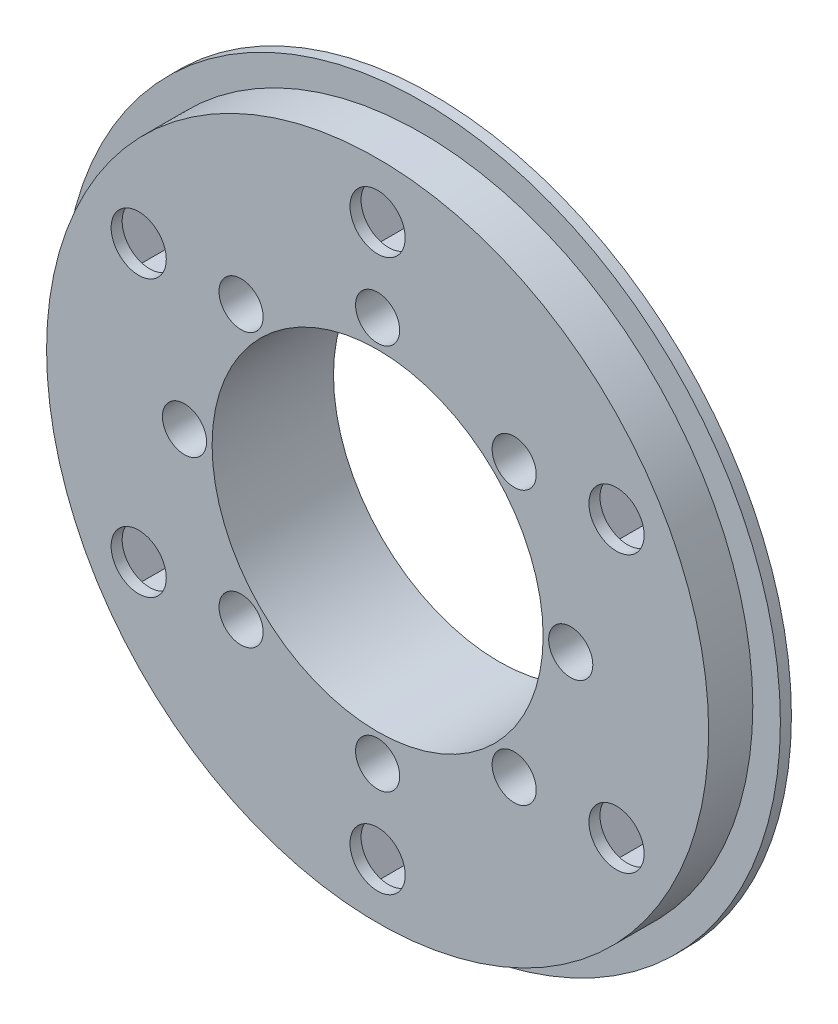
SolidWorks part; units mm, degrees
ref_plane "Front Plane" through (0, 0, 0) normal (0, 0, 1) x (1, 0, 0)
ref_plane "Top Plane" through (0, 0, 0) normal (0, 1, 0) x (1, 0, 0)
ref_plane "Right Plane" through (0, 0, 0) normal (1, 0, 0) x (0, 0, -1)
sketch "Sketch1" plane through (0, 0, 0) normal (0, 0, 1) x (1, 0, 0)
  circle A0 centre (0, 0) radius 20
  dimension "D1" = 40
extrude "Boss-Extrude1" add sketch "Sketch1" along normal blind 6
sketch "Sketch2" plane through (0, 0, 6) normal (0, 0, 1) x (1, 0, 0)
  circle A0 centre (0, 17.5) radius 2
  circle A1 centre (12.3744, 12.3744) radius 2
  circle A2 centre (17.5, 0) radius 2
  circle A3 centre (12.3744, -12.3744) radius 2
  circle A4 centre (0, -17.5) radius 2
  circle A5 centre (-12.3744, -12.3744) radius 2
  circle A6 centre (-17.5, 0) radius 2
  circle A7 centre (-12.3744, 12.3744) radius 2
  point P20 (0, 0)
  dimension "D1" = 4
  dimension "D2" = 17.5
  dimension "D3" = 8
extrude "Cut-Extrude1" cut sketch "Sketch2" against normal through all and the other way blind 7
sketch "Sketch3" plane through (0, 0, 0) normal (0, 0, -1) x (-1, 0, 0)
  circle A0 centre (0, 0) radius 15
  dimension "D1" = 30
extrude "Cut-Extrude2" cut sketch "Sketch3" against normal blind 6
sketch "Sketch4" plane through (0, 0, 6) normal (0, 0, 1) x (1, 0, 0)
  circle A0 centre (0, 0) radius 15
  circle A1 centre (0, 0) radius 30
  dimension "D1" = 60
extrude "Boss-Extrude2" add sketch "Sketch4" along normal blind 5
sketch "Sketch6" plane through (0, 0, 6) normal (0, 0, -1) x (-1, 0, 0)
  circle A0 centre (0, 17.5) radius 2
  circle A1 centre (12.3744, 12.3744) radius 2
  circle A2 centre (17.5, 0) radius 2
  circle A3 centre (12.3744, -12.3744) radius 2
  circle A4 centre (0, -17.5) radius 2
  circle A5 centre (-12.3744, -12.3744) radius 2
  circle A6 centre (-17.5, 0) radius 2
  circle A7 centre (-12.3744, 12.3744) radius 2
  point P19 (0, 0)
  dimension "D1" = 8
extrude "Cut-Extrude3" cut sketch "Sketch6" against normal blind 7
sketch "Sketch7" plane through (0, 0, 6) normal (0, 0, -1) x (-1, 0, 0)
  line L0 (23.96, 8.5) -> (26.2694, 12.5)
  line L1 (4.6188, 25) -> (2.3094, 29)
  line L2 (2.3094, 29) -> (-2.3094, 29)
  line L3 (-2.3094, 29) -> (-4.6188, 25)
  line L4 (-4.6188, 25) -> (-2.3094, 21)
  line L5 (-2.3094, 21) -> (2.3094, 21)
  line L6 (2.3094, 21) -> (4.6188, 25)
  line L7 (26.2694, 12.5) -> (23.96, 16.5)
  line L8 (23.96, 16.5) -> (19.3412, 16.5)
  line L9 (19.3412, 16.5) -> (17.0318, 12.5)
  line L10 (17.0318, 12.5) -> (19.3412, 8.5)
  line L11 (19.3412, 8.5) -> (23.96, 8.5)
  line L12 (19.3412, -16.5) -> (23.96, -16.5)
  line L13 (23.96, -16.5) -> (26.2694, -12.5)
  line L14 (26.2694, -12.5) -> (23.96, -8.5)
  line L15 (23.96, -8.5) -> (19.3412, -8.5)
  line L16 (19.3412, -8.5) -> (17.0318, -12.5)
  line L17 (17.0318, -12.5) -> (19.3412, -16.5)
  line L18 (-4.6188, -25) -> (-2.3094, -29)
  line L19 (-2.3094, -29) -> (2.3094, -29)
  line L20 (2.3094, -29) -> (4.6188, -25)
  line L21 (4.6188, -25) -> (2.3094, -21)
  line L22 (2.3094, -21) -> (-2.3094, -21)
  line L23 (-2.3094, -21) -> (-4.6188, -25)
  line L24 (-23.96, -8.5) -> (-26.2694, -12.5)
  line L25 (-26.2694, -12.5) -> (-23.96, -16.5)
  line L26 (-23.96, -16.5) -> (-19.3412, -16.5)
  line L27 (-19.3412, -16.5) -> (-17.0318, -12.5)
  line L28 (-17.0318, -12.5) -> (-19.3412, -8.5)
  line L29 (-19.3412, -8.5) -> (-23.96, -8.5)
  line L30 (-19.3412, 16.5) -> (-23.96, 16.5)
  line L31 (-23.96, 16.5) -> (-26.2694, 12.5)
  line L32 (-26.2694, 12.5) -> (-23.96, 8.5)
  line L33 (-23.96, 8.5) -> (-19.3412, 8.5)
  line L34 (-19.3412, 8.5) -> (-17.0318, 12.5)
  line L35 (-17.0318, 12.5) -> (-19.3412, 16.5)
  circle A0 centre (0, 25) radius 4 construction
  point P41 (0, 0)
  dimension "D1" = 25
  dimension "D2" = 8
  dimension "D3" = 6
extrude "Cut-Extrude4" cut sketch "Sketch7" against normal blind 4
sketch "Sketch8" plane through (0, 0, 10) normal (0, 0, -1) x (-1, 0, 0)
  circle A0 centre (0, 25) radius 2.5
  circle A1 centre (21.6506, 12.5) radius 2.5
  circle A2 centre (21.6506, -12.5) radius 2.5
  circle A3 centre (0, -25) radius 2.5
  circle A4 centre (-21.6506, -12.5) radius 2.5
  circle A5 centre (-21.6506, 12.5) radius 2.5
  point P14 (0, 0)
  dimension "D1" = 5
  dimension "D2" = 6
extrude "Cut-Extrude5" cut sketch "Sketch8" against normal blind 4
sketch "Sketch9" plane through (0, 0, 6) normal (0, 0, -1) x (-1, 0, 0)
  circle A0 centre (0, 0) radius 30
  circle A1 centre (0, 0) radius 32.5
  dimension "D1" = 65
extrude "Boss-Extrude3" add sketch "Sketch9" against normal blind 1
